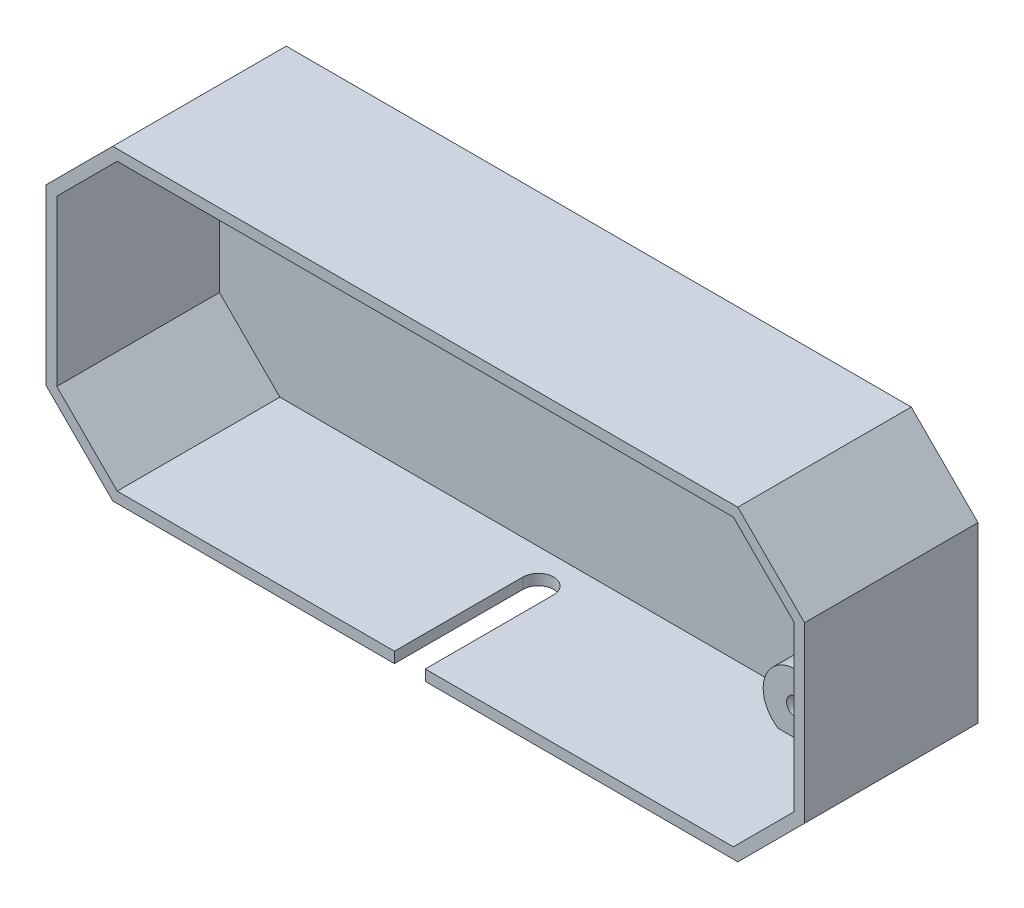
SolidWorks part; units mm, degrees
ref_plane "Front Plane" through (0, 0, 0) normal (0, 0, 1) x (1, 0, 0)
ref_plane "Top Plane" through (0, 0, 0) normal (0, 1, 0) x (1, 0, 0)
ref_plane "Right Plane" through (0, 0, 0) normal (1, 0, 0) x (0, 0, -1)
sketch "Sketch1" plane through (0, 0, 0) normal (0, 0, 1) x (1, 0, 0)
  line L1 (-28.1304, -11.3918) -> (28.1304, -11.3918)
  line L2 (-28.1304, -11.3918) -> (-28.1304, 11.3918)
  line L3 (-28.1304, 11.3918) -> (28.1304, 11.3918)
  line L4 (28.1304, -11.3918) -> (28.1304, 11.3918)
  line L5 (-28.1304, -11.3918) -> (28.1304, 11.3918) construction
  line L6 (-28.1304, 11.3918) -> (28.1304, -11.3918) construction
  point P0 (0, 0)
  dimension "D1" = 56.2608
  dimension "D2" = 22.7836
extrude "Boss-Extrude1" add sketch "Sketch1" along normal blind 0.8
sketch "Sketch2" plane through (0, 0, 0.8) normal (0, 0, 1) x (1, 0, 0)
  line L0 (-28.1304, -6.4421) -> (-23.1807, -11.3918)
  line L1 (-28.1304, 11.3918) -> (-28.1304, -11.3918) construction
  line L2 (-28.1304, 6.4421) -> (-23.1807, 11.3918)
  line L3 (28.1304, 11.3918) -> (-28.1304, 11.3918) construction
  line L4 (-23.1807, 11.3918) -> (-28.1304, 11.3918)
  line L5 (-28.1304, 11.3918) -> (-28.1304, 6.4421)
  line L6 (-28.1304, -11.3918) -> (28.1304, -11.3918) construction
  line L7 (-23.1807, -11.3918) -> (-28.1304, -11.3918)
  line L8 (-28.1304, -11.3918) -> (-28.1304, -6.4421)
  line L9 (23.1807, -11.3918) -> (28.1304, -6.4421)
  line L10 (28.1304, -11.3918) -> (28.1304, 11.3918) construction
  line L11 (28.1304, -6.4421) -> (28.1304, -11.3918)
  line L12 (28.1304, -11.3918) -> (23.1807, -11.3918)
  line L13 (23.1807, 11.3918) -> (28.1304, 6.4421)
  line L14 (28.1304, 6.4421) -> (28.1304, 11.3918)
  line L15 (28.1304, 11.3918) -> (23.1807, 11.3918)
  dimension "D1" = 7
  dimension "D2" = 7
  dimension "D3" = 7
  dimension "D4" = 7
  dimension "D5" = 45
  dimension "D6" = 45
  dimension "D7" = 45
  dimension "D8" = 45
extrude "Cut-Extrude1" cut sketch "Sketch2" against normal through all
sketch "Sketch3" plane through (0, 0, 0.8) normal (0, 0, 1) x (1, 0, 0)
  line L0 (23.1807, 11.3918) -> (-23.1807, 11.3918)
  line L1 (-23.1807, 11.3918) -> (-28.1304, 6.4421)
  line L2 (-28.1304, 6.4421) -> (-28.1304, -6.4421)
  line L3 (-28.1304, -6.4421) -> (-23.1807, -11.3918)
  line L4 (-23.1807, -11.3918) -> (23.1807, -11.3918)
  line L5 (23.1807, -11.3918) -> (28.1304, -6.4421)
  line L6 (28.1304, -6.4421) -> (28.1304, 6.4421)
  line L7 (28.1304, 6.4421) -> (23.1807, 11.3918)
  line L48 (-22.8493, 10.5918) -> (-27.3304, 6.1107)
  line L49 (-27.3304, 6.1107) -> (-27.3304, -6.1107)
  line L50 (-27.3304, -6.1107) -> (-22.8493, -10.5918)
  line L51 (-22.8493, -10.5918) -> (22.8493, -10.5918)
  line L52 (22.8493, -10.5918) -> (27.3304, -6.1107)
  line L53 (27.3304, -6.1107) -> (27.3304, 6.1107)
  line L54 (27.3304, 6.1107) -> (22.8493, 10.5918)
  line L55 (22.8493, 10.5918) -> (-22.8493, 10.5918)
  line L56 (-22.8493, 10.5918) -> (-27.3304, 6.1107)
  line L57 (-27.3304, 6.1107) -> (-27.3304, -6.1107)
  line L58 (-27.3304, -6.1107) -> (-22.8493, -10.5918)
  line L59 (-22.8493, -10.5918) -> (22.8493, -10.5918)
  line L60 (22.8493, -10.5918) -> (27.3304, -6.1107)
  line L61 (27.3304, -6.1107) -> (27.3304, 6.1107)
  line L62 (27.3304, 6.1107) -> (22.8493, 10.5918)
  line L63 (22.8493, 10.5918) -> (-22.8493, 10.5918)
  dimension "D1" = 0.8
  dimension "D2" = 0.8
extrude "Boss-Extrude2" add sketch "Sketch3" along normal blind 12.065
sketch "Sketch4" plane through (0, 0, 0.8) normal (0, 0, 1) x (1, 0, 0)
  line L0 (22.8493, 10.5918) -> (-22.8493, 10.5918) construction
  line L1 (-22.8493, -10.5918) -> (22.8493, -10.5918) construction
  line L2 (-27.3304, 6.1107) -> (-27.3304, -6.1107) construction
  circle A0 centre (-21.7424, 8.5598) radius 2.413
  circle A1 centre (18.203, -8.5598) radius 2.413
  dimension "D1" = 4.826
  dimension "D2" = 4.826
  dimension "D3" = 2.032
  dimension "D4" = 2.032
  dimension "D5" = 43.4594
  dimension "D6" = 5.588
extrude "Boss-Extrude3" add sketch "Sketch4" along normal blind 2.794
sketch "Sketch5" plane through (0, 0, 3.594) normal (0, 0, 1) x (1, 0, 0)
  circle A0 centre (-21.7424, 8.5598) radius 0.6731
  circle A1 centre (18.203, -8.5598) radius 0.6731
  dimension "D1" = 1.3462
  dimension "D2" = 1.3462
extrude "Cut-Extrude2" cut sketch "Sketch5" against normal up to surface (2.794 mm away) up to face at (1.4579, -1.0039, 0.8)
sketch "Sketch6" plane through (0, -11.3918, 0) normal (0, -1, 0) x (-1, 0, 0)
  line L0 (2.286, -12.865) -> (2.286, -3.34)
  line L1 (23.1807, -12.865) -> (-23.1807, -12.865) construction
  line L2 (0, -12.865) -> (2.286, -12.865)
  line L3 (0, -3.34) -> (0, -12.865)
  arc A0 (2.286, -3.34) -> (0, -3.34) centre (1.143, -3.34) ccw
  dimension "D2" = 1.143
  dimension "D1" = 2.286
  dimension "D3" = 9.525
extrude "Cut-Extrude3" cut sketch "Sketch6" against normal blind 2.794
